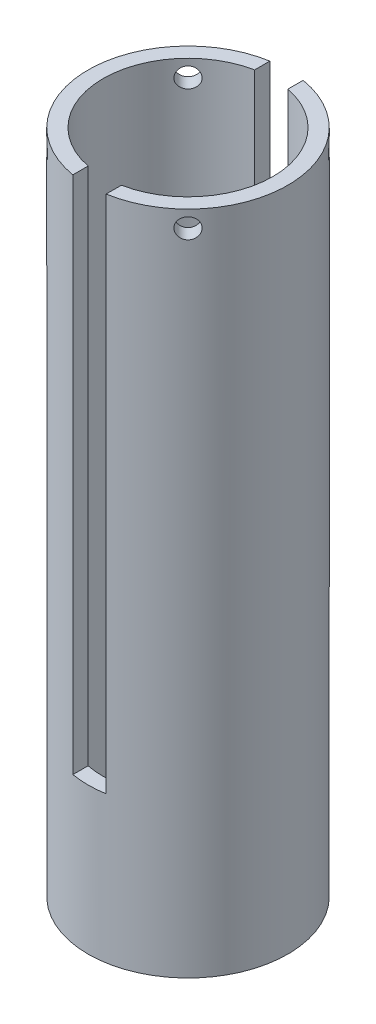
SolidWorks part; units mm, degrees
material "Brass"
ref_plane "Front Plane" through (0, 0, 0) normal (0, 0, 1) x (1, 0, 0)
ref_plane "Top Plane" through (0, 0, 0) normal (0, 1, 0) x (1, 0, 0)
ref_plane "Right Plane" through (0, 0, 0) normal (1, 0, 0) x (0, 0, -1)
sketch "Sketch1" plane through (0, 0, 0) normal (0, 1, 0) x (1, 0, 0)
  circle A0 centre (0, 0) radius 3
  circle A1 centre (0, 0) radius 2.55
  dimension "D1" = 6
  dimension "D2" = 0.45
extrude "Boss-Extrude1" add sketch "Sketch1" along normal blind 20
sketch "Sketch2" plane through (0, 0, 0) normal (0, 0, 1) x (1, 0, 0)
  line L0 (2.55, 20) -> (-2.55, 20) construction
  line L1 (-0.5, 20) -> (0.5, 20)
  line L2 (-0.5, 20) -> (-0.5, 4.4)
  line L3 (-0.5, 4.4) -> (0.5, 4.4)
  line L4 (0.5, 20) -> (0.5, 4.4)
  line L5 (-0.5, 20) -> (0.5, 4.4) construction
  line L6 (-0.5, 4.4) -> (0.5, 20) construction
  point P0 (0, 12.2)
  dimension "D1" = 15.6
  dimension "D2" = 1
extrude "Cut-Extrude1" cut sketch "Sketch2" against normal through all and the other way through all
hole_wizard "Ø0.6 (0.6) Diameter Hole1" positions "3DSketch1" profile "Sketch3" hole size "Ø0.6" standard "ANSI Metric" end condition up to next
sketch3d "3DSketch1"
  line L0 (0, 20, 0) -> (0, 19.5, 0) construction
  line L1 (0, 19.5, 0) -> (2.1213, 19.5, -2.1213) construction
  line L4 (0, 19.5, 0) -> (2.1213, 19.5, 2.1213) construction
  line L5 (2.1213, 19.5, 2.1213) -> (2.1213, 19.5, -2.1213) construction
  line L6 (0, 19.5, 0) -> (-2.1213, 19.5, 2.1213) construction
  line L9 (0, 19.5, 0) -> (-2.1213, 19.5, -2.1213) construction
  arc A0 (-0.5, 20, -2.958) -> (-0.5, 20, 2.958) centre (0, 20, 0) ccw construction
  point P15 (0, 23, 0)
  point P16 (2.1213, 19.5, 2.1213)
  point P18 (2.1213, 19.5, -2.1213)
  point P29 (-2.1213, 19.5, 2.1213)
  point P31 (-2.1213, 19.5, -2.1213)
  dimension "D1" = 0.5
sketch "Sketch3" plane through (2.1213, 19.5, 2.1213) normal (0, 1, 0) x (0.7071, 0, -0.7071)
  line L0 (0, 0) -> (0, 0.45)
  line L1 (0, 0.45) -> (0.3, 0.45)
  line L2 (0.3, 0.45) -> (0.3, 0)
  line L5 (0.3, 0) -> (0, 0)
  line L11 (0, -6.35) -> (0, 107.95) construction
  dimension "Thru Hole Dia." = 0.6
  dimension "Thru Hole Depth" = 0.45
